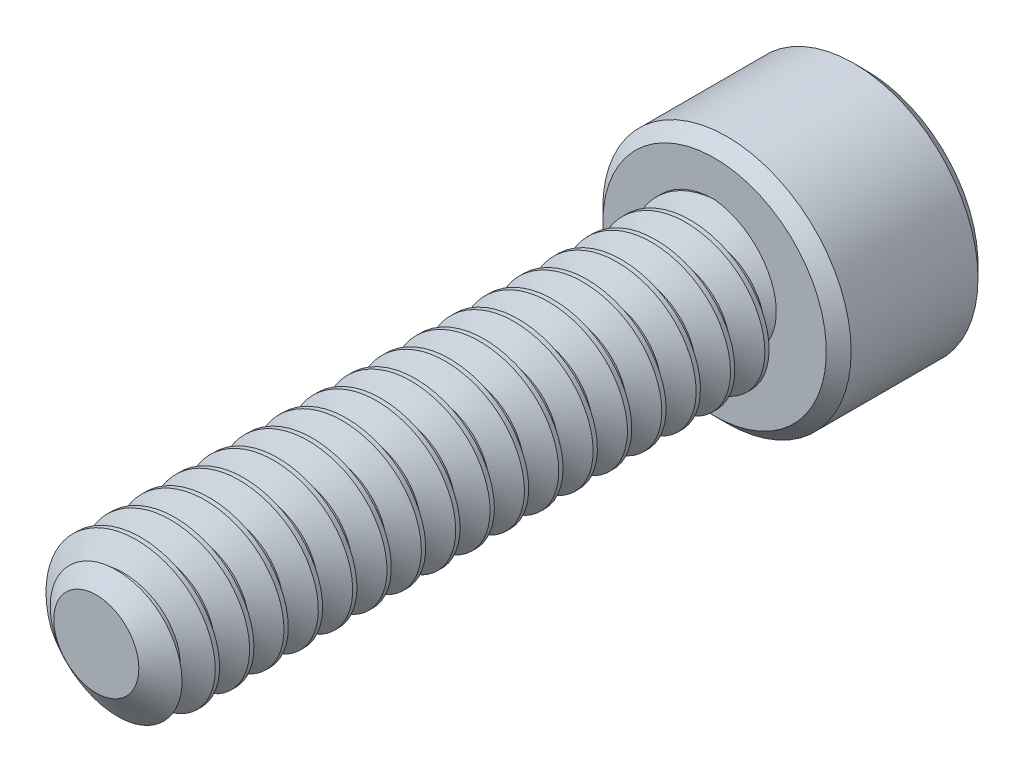
SolidWorks part; units mm, degrees
ref_plane "Front Plane" through (0, 0, 0) normal (0, 0, 1) x (1, 0, 0)
ref_plane "Top Plane" through (0, 0, 0) normal (0, 1, 0) x (1, 0, 0)
ref_plane "Right Plane" through (0, 0, 0) normal (1, 0, 0) x (0, 0, -1)
sketch "Sketch1" plane through (0, 0, 0) normal (0, 0, 1) x (1, 0, 0)
  circle A0 centre (0, 0) radius 1.7526
  dimension "OD" = 3.5052
extrude "Extrude1" add sketch "Sketch1" against normal blind 14.2875
sketch "Sketch2" plane through (0, 0, 0) normal (0, 0, 1) x (1, 0, 0)
  circle A0 centre (0, 0) radius 1.7526 construction
  circle A1 centre (0, 0) radius 1.7526
curve "Helix/Spiral1" pitch 0.7937 height 15.0812 turns 19 parameters "pitch"=0.7937
sketch "Sketch3" plane through (0, 0, 0) normal (1, 0, 0) x (0, 0, -1)
  line L0 (-0.6945, 1.7526) -> (-0.3969, 1.237)
  line L1 (-0.3969, 1.237) -> (-0.2977, 1.237)
  line L2 (-0.2977, 1.237) -> (0, 1.7526)
  line L3 (-0.6945, 1.7526) -> (0, 1.7526)
  line L4 (-0.3473, 1.7526) -> (-0.3473, 1.237) construction
  line L5 (-0.5457, 1.4948) -> (-0.1488, 1.4948) construction
  line L6 (0, 1.7526) -> (0, -1.7526) construction
  dimension "D1" = 0.0992
  dimension "D2" = 0.3969
  dimension "D3" = 60
sweep "Cut-Sweep1" cut profiles "Sketch3" path "Helix/Spiral1"
sketch "Sketch4" plane through (0, 0, 0) normal (1, 0, 0) x (0, 0, -1)
  line L0 (0.5388, 1.7526) -> (0, 0.983)
  line L1 (0, 0.983) -> (0, 1.7526)
  line L2 (0.5388, 1.7526) -> (0, 1.7526)
  line L3 (-0.6945, 1.7526) -> (0, 1.7526) construction
  line L4 (0, 0) -> (7.0209, 0) construction
  dimension "D1" = 55
  dimension "D2" = 0.254
revolve "Cut-Revolve1" cut sketch "Sketch4" angle 360 about L4
sketch "Sketch5" plane through (0, 0, 0) normal (1, 0, 0) x (0, 0, -1)
  line L0 (14.2875, -1.2539) -> (14.2875, 1.2505) construction
  line L1 (14.2875, 1.8796) -> (0.1202, 1.8796)
  line L2 (14.2875, 1.8796) -> (14.2875, 0)
  line L3 (14.2875, 0) -> (0, 0)
  line L4 (0, 1.5494) -> (0, 0)
  line L5 (0.1202, 1.8796) -> (0, 1.5494)
  line L6 (0, 0) -> (9.9695, 0) construction
  point P3 (0, 1.8796)
  point P10 (0, 1.8796)
  dimension "D1" = 0.3302
  dimension "D2" = 0.127
  dimension "D3" = 20
  dimension "Min Thread" = 0
revolve "partially thread" [suppressed] add sketch "Sketch5" angle 360 about L6
sketch "Sketch6" plane through (0, 0, -14.2875) normal (0, 0, -1) x (-1, 0, 0)
  circle A0 centre (0, 0) radius 2.8702
  dimension "head dia" = 5.7404
extrude "Extrude2" add sketch "Sketch6" along normal blind 3.5052
sketch "Sketch7" plane through (0, 0, -17.7927) normal (0, 0, -1) x (-1, 0, 0)
  line L1 (0, 1.604) -> (-1.3891, 0.802)
  line L2 (-1.3891, 0.802) -> (-1.3891, -0.802)
  line L3 (-1.3891, -0.802) -> (0, -1.604)
  line L4 (0, -1.604) -> (1.3891, -0.802)
  line L5 (1.3891, -0.802) -> (1.3891, 0.802)
  line L6 (1.3891, 0.802) -> (0, 1.604)
  circle A0 centre (0, 0) radius 1.3891 construction
  dimension "hex dia" = 2.7781
extrude "Cut-Extrude1" cut sketch "Sketch7" against normal blind 2.0836
sketch "Sketch8" plane through (0, 0, -17.7927) normal (0, 0, -1) x (-1, 0, 0)
  circle A0 centre (0, 0) radius 1.604
extrude "Cut-Extrude2" cut sketch "Sketch8" against normal through all draft 45
chamfer "Chamfer1" distance 0.287 angle 45 2 edges at (-2.8702, 0, -17.7927) (-2.8702, 0, -14.2875)
sketch "Sketch9" plane through (0, 0, 0) normal (1, 0, 0) x (0, 0, -1)
  line L0 (0, 1.7526) -> (0, -1.7526) construction
  line L1 (1.9844, 1.7526) -> (1.9844, -1.7526) construction
  dimension "D1" = 1.9844
equation "\"D3@Helix/Spiral1\" = \"screw length@Extrude1\"+\"pitch@Helix/Spiral1\""
equation "\"D1@Sketch3\" = \"pitch@Helix/Spiral1\"*.125"
equation "\"D2@Sketch3\" = \"pitch@Helix/Spiral1\"*.5"
equation "\"D1@Cut-Extrude1\" = \"hex dia@Sketch7\"*.75"
equation "\"D1@Chamfer1\" = \"head dia@Sketch6\"*.05"
equation "\"D1@Sketch9\" = \"pitch@Helix/Spiral1\"*2.5"
